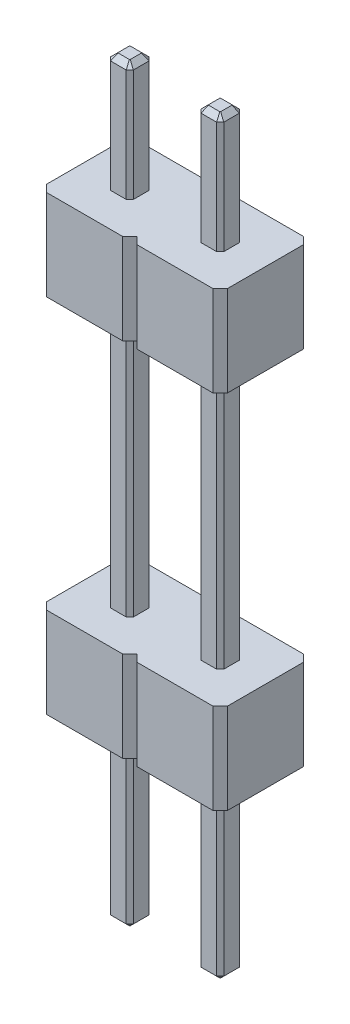
SolidWorks part; units mm, degrees
ref_plane "Спереди" through (0, 0, 0) normal (0, 0, 1) x (1, 0, 0)
ref_plane "Сверху" through (0, 0, 0) normal (0, 1, 0) x (1, 0, 0)
ref_plane "Справа" through (0, 0, 0) normal (1, 0, 0) x (0, 0, -1)
sketch "Эскиз1" plane through (0, 0, 0) normal (0, 1, 0) x (1, 0, 0)
  line L0 (0, 0) -> (0, 5470.6329) construction
  line L1 (0, 0) -> (-5470.6329, 0) construction
  line L2 (-1.59, 0.22) -> (-1.49, 0.32)
  line L3 (-1.49, -0.32) -> (-1.05, -0.32)
  line L4 (-1.59, -0.22) -> (-1.59, 0.22)
  line L5 (-1.49, 0.32) -> (-1.05, 0.32)
  line L6 (-0.95, -0.22) -> (-0.95, 0.22)
  line L7 (-1.59, -0.32) -> (-0.95, 0.32) construction
  line L8 (-1.59, 0.32) -> (-0.95, -0.32) construction
  line L9 (-2.34, 1.27) -> (-0.2, 1.27)
  line L10 (-2.54, 1.07) -> (-2.54, -1.07)
  line L11 (-2.34, -1.27) -> (-0.2, -1.27)
  line L12 (0, 1.07) -> (0, -1.07)
  line L13 (-2.54, 1.27) -> (0, -1.27) construction
  line L14 (-2.54, -1.27) -> (0, 1.27) construction
  line L15 (-1.05, 0.32) -> (-0.95, 0.22)
  line L16 (-1.05, -0.32) -> (-0.95, -0.22)
  line L17 (-1.59, -0.22) -> (-1.49, -0.32)
  line L18 (-2.54, 1.07) -> (-2.34, 1.27)
  line L19 (-0.2, 1.27) -> (0, 1.07)
  line L20 (-0.2, -1.27) -> (0, -1.07)
  line L21 (-2.54, -1.07) -> (-2.34, -1.27)
  line L22 (0.95, 0.22) -> (1.05, 0.32)
  line L23 (1.05, -0.32) -> (1.49, -0.32)
  line L24 (0.95, -0.22) -> (0.95, 0.22)
  line L25 (1.05, 0.32) -> (1.49, 0.32)
  line L26 (1.59, -0.22) -> (1.59, 0.22)
  line L27 (0.2, 1.27) -> (2.34, 1.27)
  line L28 (0, 1.07) -> (0, -1.07)
  line L29 (0.2, -1.27) -> (2.34, -1.27)
  line L30 (2.54, 1.07) -> (2.54, -1.07)
  line L31 (1.49, 0.32) -> (1.59, 0.22)
  line L32 (1.49, -0.32) -> (1.59, -0.22)
  line L33 (0.95, -0.22) -> (1.05, -0.32)
  line L34 (0, 1.07) -> (0.2, 1.27)
  line L35 (2.34, 1.27) -> (2.54, 1.07)
  line L36 (2.34, -1.27) -> (2.54, -1.07)
  line L37 (0, -1.07) -> (0.2, -1.27)
  line L38 (0.95, -0.32) -> (1.59, 0.32) construction
  line L39 (0.95, 0.32) -> (1.59, -0.32) construction
  line L40 (0, 1.27) -> (2.54, -1.27) construction
  line L41 (0, -1.27) -> (2.54, 1.27) construction
  point P5 (-1.27, 0)
  point P10 (-1.27, 0)
  point P31 (1.4986, 0.3755)
  point P33 (1.27, 0)
  point P38 (1.27, 0)
  dimension "D1" = 0.64
  dimension "D2" = 1.27
  dimension "D3" = 2
extrude "Бобышка-Вытянуть1" add sketch "Эскиз1" against normal blind 5.08 contours L4 L17 L3 L16 L6 L15 L5 L2 | L24 L33 L23 L32 L26 L31 L25 L22 region at (-1.27, 0, 0) region at (1.27, 0, 0)
extrude "Бобышка-Вытянуть2" add sketch "Эскиз1<3>" along normal blind 16 contours L4 L17 L3 L16 L6 L15 L5 L2 | L24 L33 L23 L32 L26 L31 L25 L22 region at (-1.27, 0, 0) region at (1.27, 0, 0)
sketch "Эскиз1<3>" plane through (0, 0, 0) normal (0, 1, 0) x (1, 0, 0) same geometry as "Эскиз1"
extrude "Бобышка-Вытянуть3" add sketch "Эскиз1<4>" along normal blind 2.54 contours L10 L21 L11 L20 L12 L19 L9 L18 L17 L4 L2 L5 L15 L6 L16 L3 | L12 L37 L29 L36 L30 L35 L27 L34 L33 L24 L22 L25 L31 L26 L32 L23 region at (-1.27, 0, -1.2341) region at (0.1254, 0, -1.1446)
sketch "Эскиз1<4>" plane through (0, 0, 0) normal (0, 1, 0) x (1, 0, 0) same geometry as "Эскиз1"
extrude "Бобышка-Вытянуть4" add sketch "Эскиз1<5>" against normal blind 2.54 from offset 12.7 contours L10 L21 L11 L20 L12 L19 L9 L18 L17 L4 L2 L5 L15 L6 L16 L3 | L12 L37 L29 L36 L30 L35 L27 L34 L33 L24 L22 L25 L31 L26 L32 L23 region at (-1.27, 0, -1.2341) region at (0.1254, 0, -1.1446)
sketch "Эскиз1<5>" plane through (0, 0, 0) normal (0, 1, 0) x (1, 0, 0) same geometry as "Эскиз1"
chamfer "Фаска1" distance 0.15 angle 45 32 edges at (-1.54, -5.08, 0.27) (-1.27, -5.08, 0.32) (-1, -5.08, 0.27) (-0.95, -5.08, 0) (-1, -5.08, -0.27) (-1.27, -5.08, -0.32) (-1.54, -5.08, -0.27) (-1.59, -5.08, 0) (1, -5.08, 0.27) (1.27, -5.08, 0.32) (1.54, -5.08, 0.27) (1.59, -5.08, 0) (1.54, -5.08, -0.27) (1.27, -5.08, -0.32) (1, -5.08, -0.27) (0.95, -5.08, 0) (1, 16, -0.27) (1.27, 16, -0.32) (1.54, 16, -0.27) (1.59, 16, 0) (1.54, 16, 0.27) (1.27, 16, 0.32) (1, 16, 0.27) (0.95, 16, 0) (-1.54, 16, -0.27) (-1.27, 16, -0.32) (-1, 16, -0.27) (-0.95, 16, 0) (-1, 16, 0.27) (-1.27, 16, 0.32) (-1.54, 16, 0.27) (-1.59, 16, 0)
